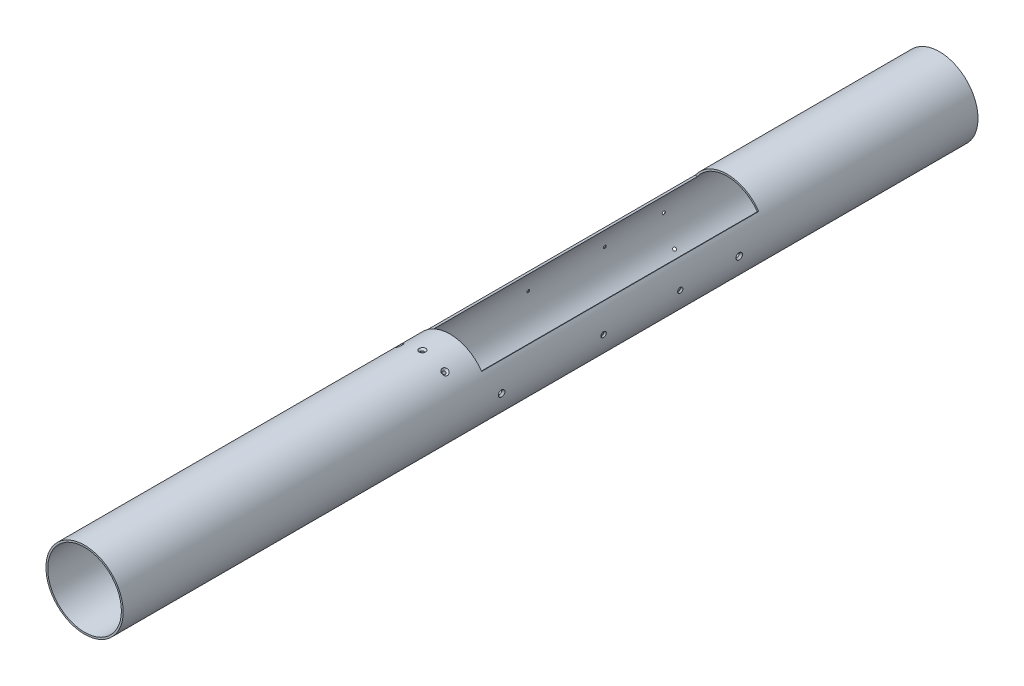
SolidWorks part; units mm, degrees
material "Cam Elyaf Real"
ref_plane "Ön Düzlem" through (0, 0, 0) normal (0, 0, 1) x (1, 0, 0)
ref_plane "Üst Düzlem" through (0, 0, 0) normal (0, 1, 0) x (1, 0, 0)
ref_plane "Sağ Düzlem" through (0, 0, 0) normal (1, 0, 0) x (0, 0, -1)
sketch "Çizim1" plane through (0, 0, 0) normal (0, 0, 1) x (1, 0, 0)
  circle A0 centre (0, 0) radius 62.5
  dimension "D1" = 125
extrude "Ekstrüzyon-İnce1" add sketch "Çizim1" along normal blind 1450 thin thin type one direction wall 3
ref_plane "Düzlem1" through (0, 65.5, 0) normal (0, 1, 0) x (1, 0, 0)
sketch "Çizim2" plane through (0, 65.5, 0) normal (0, 1, 0) x (1, 0, 0)
  line L0 (0, -1450) -> (0, -877) construction
  line L1 (-65.5, -1450) -> (65.5, -1450) construction
  point P1 (0, -877)
  point P8 (0, -877)
  dimension "D1" = 573
hole_wizard "M5 Altıgen Alyan Havşa Başlı Kör Vida İçin Havşa3" positions "Çizim2" profile "Çizim3" countersink size "M5" standard "ISO"
sketch "Çizim3" plane through (0, 65.5, 877) normal (1, 0, 0) x (0, 0, 1)
  line L0 (0, 0) -> (0, 13.8923)
  line L1 (0, 13.8923) -> (2.65, 12.3)
  line L2 (2.65, 12.3) -> (2.65, 2.95)
  line L3 (2.65, 2.95) -> (5.6, 0)
  line L5 (5.6, 0) -> (0, 0)
  line L6 (-2.65, 2.95) -> (-5.6, 0) construction
  line L10 (0, 13.8923) -> (-2.65, 12.3) construction
  line L11 (0, -6.35) -> (0, 107.95) construction
  dimension "Hole Dia." = 5.3
  dimension "Hole Depth" = 12.3
  dimension "Near C'Sink Dia." = 11.2
  dimension "Near C'Sink Angle" = 90
  dimension "Drill Angle" = 118
pattern_circular "Dairesel Kaplama1" count 10 over 360 about axis through (0, 0, 1450) along (0, 0, 1) skipping 2, 3, 7, 8 of "M5 Altıgen Alyan Havşa Başlı Kör Vida İçin Havşa3"
sketch "Çizim5" plane through (0, 65.5, 0) normal (0, 1, 0) x (1, 0, 0)
  line L0 (0, -1450) -> (0, -808) construction
  line L1 (-65.5, -1450) -> (65.5, -1450) construction
  point P1 (0, -808)
  point P8 (0, -808)
  dimension "D1" = 642
hole_wizard "M5 Altıgen Alyan Havşa Başlı Kör Vida İçin Havşa1" positions "Çizim5" profile "Çizim6" countersink size "M5" standard "ISO"
sketch "Çizim6" plane through (0, 65.5, 808) normal (1, 0, 0) x (0, 0, 1)
  line L0 (0, 0) -> (0, 13.8923)
  line L1 (0, 13.8923) -> (2.65, 12.3)
  line L2 (2.65, 12.3) -> (2.65, 2.95)
  line L3 (2.65, 2.95) -> (5.6, 0)
  line L5 (5.6, 0) -> (0, 0)
  line L6 (-2.65, 2.95) -> (-5.6, 0) construction
  line L10 (0, 13.8923) -> (-2.65, 12.3) construction
  line L11 (0, -6.35) -> (0, 107.95) construction
  dimension "Hole Dia." = 5.3
  dimension "Hole Depth" = 12.3
  dimension "Near C'Sink Dia." = 11.2
  dimension "Near C'Sink Angle" = 90
  dimension "Drill Angle" = 118
pattern_circular "Dairesel Kaplama2" count 8 over 360 about axis through (0, 0, 1450) along (0, 0, 1) of "M5 Altıgen Alyan Havşa Başlı Kör Vida İçin Havşa1"
sketch "Çizim7" plane through (0, 65.5, 0) normal (0, 1, 0) x (1, 0, 0)
  line L0 (0, -1450) -> (0, -405) construction
  line L1 (-65.5, -1450) -> (65.5, -1450) construction
  point P1 (0, -405)
  point P8 (0, -405)
  dimension "D1" = 1045
hole_wizard "M5 Altıgen Alyan Havşa Başlı Kör Vida İçin Havşa2" positions "Çizim7" profile "Çizim8" countersink size "M5" standard "ISO"
sketch "Çizim8" plane through (0, 65.5, 405) normal (1, 0, 0) x (0, 0, 1)
  line L0 (0, 0) -> (0, 13.8923)
  line L1 (0, 13.8923) -> (2.65, 12.3)
  line L2 (2.65, 12.3) -> (2.65, 2.95)
  line L3 (2.65, 2.95) -> (5.6, 0)
  line L5 (5.6, 0) -> (0, 0)
  line L6 (-2.65, 2.95) -> (-5.6, 0) construction
  line L10 (0, 13.8923) -> (-2.65, 12.3) construction
  line L11 (0, -6.35) -> (0, 107.95) construction
  dimension "Hole Dia." = 5.3
  dimension "Hole Depth" = 12.3
  dimension "Near C'Sink Dia." = 11.2
  dimension "Near C'Sink Angle" = 90
  dimension "Drill Angle" = 118
pattern_circular "Dairesel Kaplama3" count 8 over 360 about axis through (0, 0, 1450) along (0, 0, 1) of "M5 Altıgen Alyan Havşa Başlı Kör Vida İçin Havşa2"
sketch "Çizim9" plane through (0, 65.5, 0) normal (0, 1, 0) x (1, 0, 0)
  line L0 (0, -1450) -> (0, -635) construction
  line L1 (-65.5, -1450) -> (65.5, -1450) construction
  line L2 (0, -1450) -> (0, -505) construction
  point P1 (0, -635)
  point P6 (0, -505)
  point P10 (0, -635)
  point P14 (0, -505)
  dimension "D1" = 815
  dimension "D2" = 945
hole_wizard "M4 Altıgen Alyan Havşa Başlı Kör Vida İçin Havşa2" positions "Çizim9" profile "Çizim10" countersink size "M4" standard "ISO"
sketch "Çizim10" plane through (0, 65.5, 505) normal (1, 0, 0) x (0, 0, 1)
  line L0 (0, 0) -> (0, 12.8519)
  line L1 (0, 12.8519) -> (2.25, 11.5)
  line L2 (2.25, 11.5) -> (2.25, 2.23)
  line L3 (2.25, 2.23) -> (4.48, 0)
  line L5 (4.48, 0) -> (0, 0)
  line L6 (-2.25, 2.23) -> (-4.48, 0) construction
  line L10 (0, 12.8519) -> (-2.25, 11.5) construction
  line L11 (0, -6.35) -> (0, 107.95) construction
  dimension "Hole Dia." = 4.5
  dimension "Hole Depth" = 11.5
  dimension "Near C'Sink Dia." = 8.96
  dimension "Near C'Sink Angle" = 90
  dimension "Drill Angle" = 118
pattern_circular "Dairesel Kaplama4" count 4 over 360 about axis through (0, 0, 1450) along (0, 0, 1) of "M4 Altıgen Alyan Havşa Başlı Kör Vida İçin Havşa2"
sketch "Çizim12" plane through (0, 0, 1450) normal (0, 0, 1) x (1, 0, 0)
  line L0 (0, 0) -> (0, 29.1789) construction
  line L1 (0, 0) -> (53.6545, 37.5693) construction
  line L2 (0, 0) -> (-53.6545, 37.5693) construction
  line L3 (-53.6545, 37.5693) -> (-51.197, 35.8485)
  line L4 (53.6545, 37.5693) -> (51.197, 35.8485)
  circle A0 centre (0, 0) radius 65.5 construction
  arc A1 (53.6545, 37.5693) -> (-53.6545, 37.5693) centre (0, 0) ccw
  arc A2 (51.197, 35.8485) -> (-51.197, 35.8485) centre (0, 0) ccw
  dimension "D1" = 55
  dimension "D2" = 55
extrude "Yükseklik-Ekstrüzyon1" add sketch "Çizim12" against normal blind 470 from offset 620 offset against normal yes
sketch "Çizim14" plane through (0, 0, 1450) normal (0, 0, 1) x (1, 0, 0)
  line L0 (0, 0) -> (0, 40.8213) construction
  line L1 (0, 0) -> (53.6545, 37.5693) construction
  line L2 (0, 0) -> (-53.6545, 37.5693) construction
  line L3 (-53.6545, 37.5693) -> (-51.197, 35.8485)
  line L4 (53.6545, 37.5693) -> (51.197, 35.8485)
  circle A0 centre (0, 0) radius 65.5 construction
  arc A1 (53.6545, 37.5693) -> (-53.6545, 37.5693) centre (0, 0) ccw
  arc A2 (51.197, 35.8485) -> (-51.197, 35.8485) centre (0, 0) ccw
  dimension "D1" = 55
  dimension "D2" = 55
extrude "Kes-Ekstrüzyon1" cut sketch "Çizim14" against normal blind 470 from offset 620 offset against normal yes
sketch "Çizim16" plane through (0, 65.5, 0) normal (0, 1, 0) x (1, 0, 0)
  line L0 (0, -830) -> (0, -880) construction
  line L1 (51.197, -830) -> (-51.197, -830) construction
  line L2 (0, -880) -> (0, -1450) construction
  line L3 (-65.5, -1450) -> (65.5, -1450) construction
  dimension "D1" = 50
ref_plane "Düzlem3" through (-65.5, 0, 0) normal (1, 0, 0) x (0, 0, -1)
sketch "Çizim20" plane through (-65.5, 0, 0) normal (1, 0, 0) x (0, 0, -1)
  line L0 (-1450, 0) -> (-1010, 0) construction
  line L1 (-1450, 65.5) -> (-1450, -65.5) construction
  circle A0 centre (-1010, 0) radius 10.5
  dimension "D2" = 21
  dimension "D1" = 440
extrude "Kes-Ekstrüzyon3" cut sketch "Çizim20" along normal blind 10
